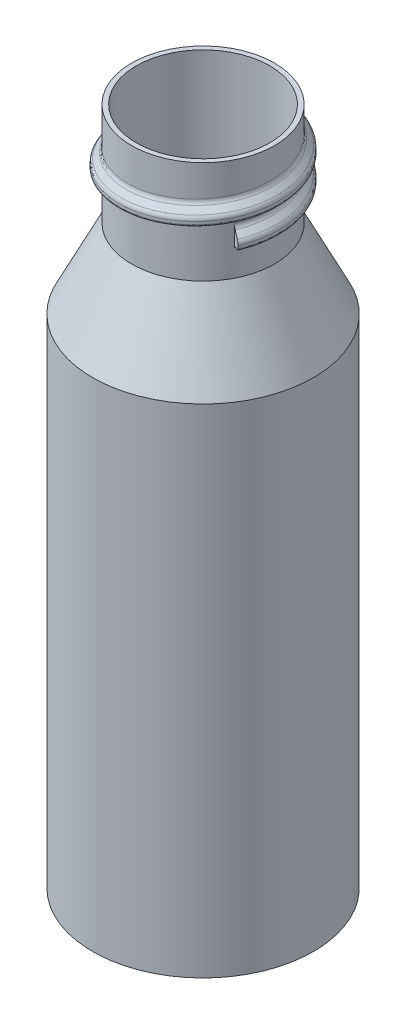
SolidWorks part; units mm, degrees
material "PET"
ref_plane "Спереди" through (0, 0, 0) normal (0, 0, 1) x (1, 0, 0)
ref_plane "Сверху" through (0, 0, 0) normal (0, 1, 0) x (1, 0, 0)
ref_plane "Справа" through (0, 0, 0) normal (1, 0, 0) x (0, 0, -1)
sketch "Эскиз2" plane through (0, 0, 0) normal (0, 0, 1) x (1, 0, 0)
  line L0 (0, 0) -> (14, 0)
  line L1 (14, 0) -> (14, 0.6)
  line L2 (14, 0.6) -> (0.6, 0.6)
  line L3 (0, 0) -> (0, 63)
  line L4 (0, 63) -> (4.9367, 73)
  line L5 (4.9367, 73) -> (4.9367, 86)
  line L6 (0.6, 0.6) -> (0.6, 63)
  line L7 (0.6, 63) -> (5.5367, 73)
  line L8 (5.5367, 73) -> (5.5367, 86)
  line L9 (5.5367, 86) -> (4.9367, 86)
  dimension "D1" = 63
  dimension "D2" = 14
  dimension "D3" = 13.4
  dimension "D4" = 0.6
  dimension "D5" = 13
  dimension "D6" = 10
  dimension "D7" = 0.6
revolve "Повернуть1" add sketch "Эскиз2" angle 360 about L1
thread "Резьба1" pitch 3.175 method extrude profile "Профиль резьбы1" start angle 0, offset 2, length 5, pitch 3.175, diameter 18.1265
ref_plane "Плоскость1" through (4.9367, 84, 0) normal (0, 0, 1) x (-1, 0, 0)
sketch "Профиль резьбы1" plane through (4.9367, 84, 0) normal (0, 0, 1) x (-1, 0, 0)
  line L0 (0, 0) -> (0, 3.175) construction
  line L1 (0, 0) -> (0, 2.6624)
  line L2 (0.254, 2.6624) -> (1.0668, 2.6624) construction
  line L3 (1.0668, 2.048) -> (1.0668, 1.6981)
  line L4 (0.8569, 2.2981) -> (0.2099, 2.4122)
  line L5 (0.8436, 1.1592) -> (0.2232, 0.5388)
  line L6 (0.762, 0) -> (1.0668, 0) construction
  arc A0 (0.2099, 2.4122) -> (0, 2.6624) centre (0.254, 2.6624) cw
  arc A1 (0.2232, 0.5388) -> (0, 0) centre (0.762, 0) ccw
  arc A2 (1.0668, 1.6981) -> (0.8436, 1.1592) centre (0.3048, 1.6981) cw
  arc A3 (1.0668, 2.048) -> (0.8569, 2.2981) centre (0.8128, 2.048) ccw
  point P10 (1.0668, 2.2611)
  point P17 (1.0668, 1.3824)
  point P18 (0, 2.4492)
  point P19 (0, 0.3156)
  point P20 (0, 0)
  dimension "RootFillet1" = 0.254
  dimension "RootFillet2" = 0.762
  dimension "CrestFillet2" = 0.762
  dimension "CrestFillet1" = 0.254
  dimension "Pitch" = 3.175
  dimension "Angle1" = 10
  dimension "Angle2" = 45
  dimension "a" = 2.1336
  dimension "b" = 1.0668
  dimension "c" = 0.8787
